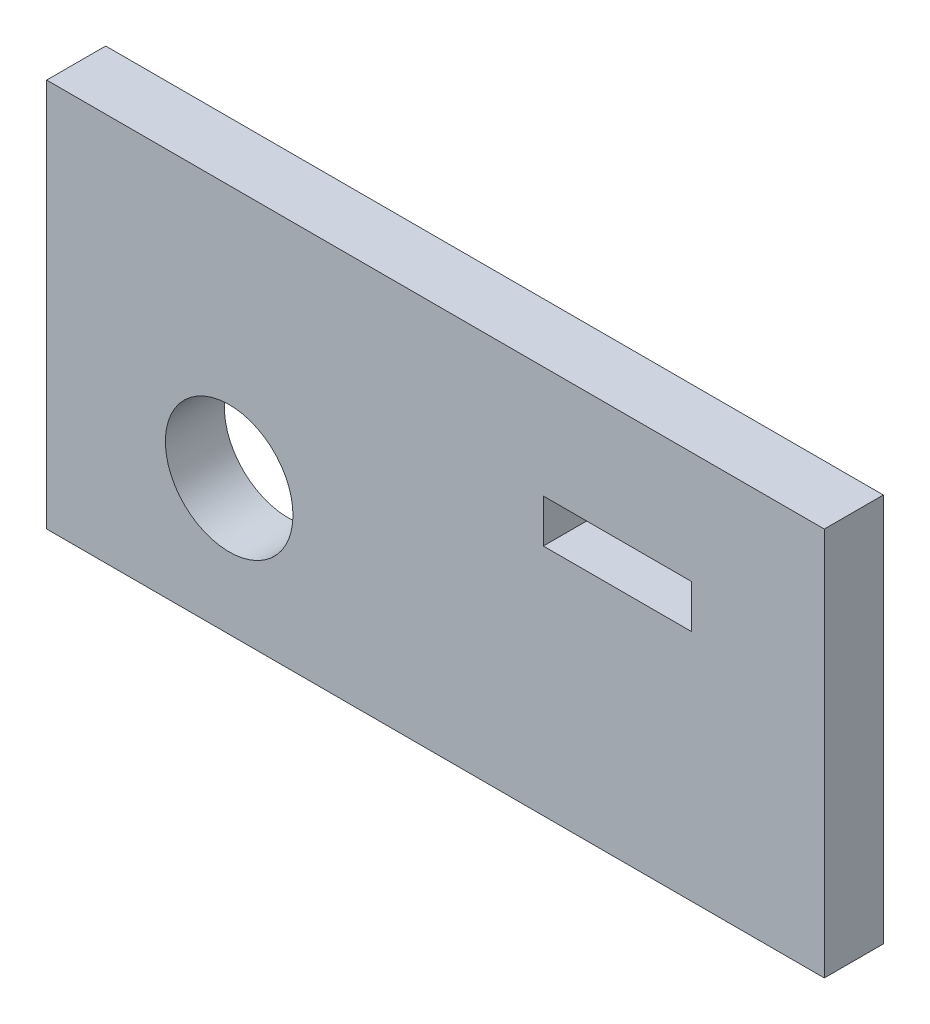
SolidWorks part; units mm, degrees
ref_plane "Front Plane" through (0, 0, 0) normal (0, 0, 1) x (1, 0, 0)
ref_plane "Top Plane" through (0, 0, 0) normal (0, 1, 0) x (1, 0, 0)
ref_plane "Right Plane" through (0, 0, 0) normal (1, 0, 0) x (0, 0, -1)
sketch "Sketch1" plane through (0, 0, 0) normal (0, 0, 1) x (1, 0, 0)
  line L1 (0, 0) -> (131.7823, 0)
  line L2 (0, 0) -> (0, 65.8912)
  line L3 (0, 65.8912) -> (131.7823, 65.8912)
  line L4 (131.7823, 0) -> (131.7823, 65.8912)
  line L5 (84.1666, 46.9356) -> (109.2895, 46.9356)
  line L6 (84.1666, 46.9356) -> (84.1666, 39.5891)
  line L7 (84.1666, 39.5891) -> (109.2895, 39.5891)
  line L8 (109.2895, 46.9356) -> (109.2895, 39.5891)
extrude "Boss-Extrude1" add sketch "Sketch1" along normal blind 10
sketch "Sketch2" plane through (0, 0, 10) normal (0, 0, 1) x (1, 0, 0)
  circle A0 centre (30.9238, 22.9153) radius 10.8112
extrude "Cut-Extrude1" cut sketch "Sketch2" against normal blind 10
